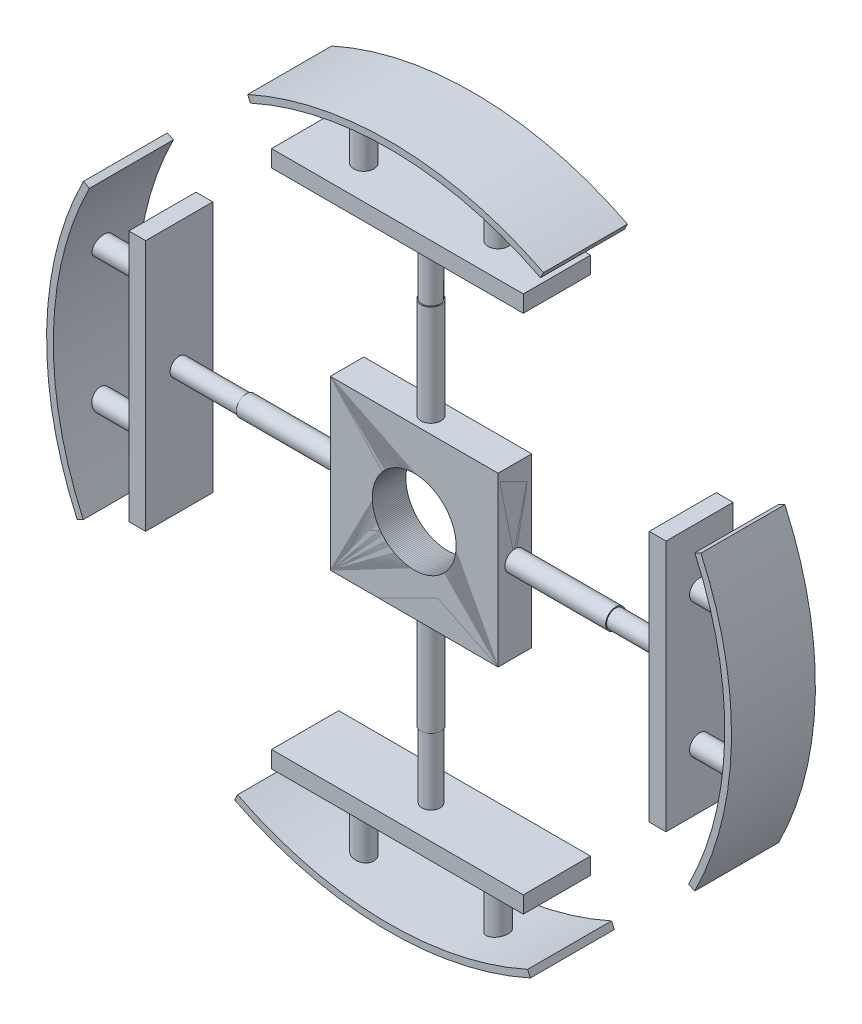
SolidWorks part; units mm, degrees
ref_plane "Front Plane" through (0, 0, 0) normal (0, 0, 1) x (1, 0, 0)
ref_plane "Top Plane" through (0, 0, 0) normal (0, 1, 0) x (1, 0, 0)
ref_plane "Right Plane" through (0, 0, 0) normal (1, 0, 0) x (0, 0, -1)
sketch "Sketch1" plane through (0, 0, 0) normal (0, 0, 1) x (1, 0, 0)
  line L1 (-25, 25) -> (25, 25)
  line L2 (-25, 25) -> (-25, -25)
  line L3 (-25, -25) -> (25, -25)
  line L4 (25, 25) -> (25, -25)
  line L5 (-25, 25) -> (25, -25) construction
  line L6 (-25, -25) -> (25, 25) construction
  point P0 (0, 0)
  dimension "D1" = 50
  dimension "D2" = 50
extrude "Boss-Extrude1" add sketch "Sketch1" along normal mid plane 10
sketch "Sketch2" plane through (0, 0, 0) normal (0, 0, 1) x (1, 0, 0)
  circle A0 centre (0, 0) radius 12.5
extrude "Cut-Extrude1" cut sketch "Sketch2" against normal mid plane 10
sketch "Sketch4" plane through (0, 25, 0) normal (0, 1, 0) x (1, 0, 0)
  circle A0 centre (0, 0) radius 3
extrude "Boss-Extrude2" add sketch "Sketch4" along normal blind 30
sketch "Sketch5" plane through (0, 55, 0) normal (0, 1, 0) x (1, 0, 0)
  circle A0 centre (0, 0) radius 2.7
extrude "Cut-Extrude2" cut sketch "Sketch5" against normal blind 30
sketch "Sketch6" plane through (0, 25, 0) normal (0, 1, 0) x (1, 0, 0)
  circle A1 centre (0, 0) radius 2.7
  circle A2 centre (0, 0) radius 2.7
  dimension "D1" = 0
extrude "Boss-Extrude3" add sketch "Sketch6" along normal blind 50
sketch "Sketch8" plane through (0, 0, 0) normal (0, 0, 1) x (1, 0, 0)
  line L0 (0, 99.0014) -> (0, -49.6038) construction
  line L3 (-37.5, 80) -> (37.5, 80)
  line L4 (-37.5, 80) -> (-37.5, 75)
  line L5 (-37.5, 75) -> (37.5, 75)
  line L6 (37.5, 80) -> (37.5, 75)
  line L7 (-37.5, 80) -> (16.5799, 76.3947) construction
  line L8 (-37.5, 75) -> (37.5, 80) construction
  point P6 (0, 77.5)
  dimension "D1" = 75
  dimension "D2" = 5
extrude "Boss-Extrude4" add sketch "Sketch8" along normal mid plane 20
sketch "Sketch9" plane through (0, 80, 0) normal (0, 1, 0) x (1, 0, 0)
  line L0 (-43.4012, 0) -> (57.5449, 0) construction
  line L1 (0, 17.0938) -> (0, -21.1348) construction
  line L2 (-20, 17.0938) -> (-20, -21.9484)
  line L3 (20, 17.0938) -> (20, -21.9604)
  circle A0 centre (-20, 0) radius 3
  circle A1 centre (20, 0) radius 3
  dimension "D1" = 20
  dimension "D2" = 20
sketch "Sketch10" plane through (0, 0, 0) normal (0, 0, 1) x (1, 0, 0)
  line L0 (46.0258, 91.0254) -> (45.1233, 89.2406)
  line L1 (-42.1017, 92.9056) -> (-41.2762, 91.0839)
  arc A0 (45.1233, 89.2406) -> (-41.2762, 91.0839) centre (0, 0) ccw
  arc A1 (46.0258, 91.0254) -> (-42.1017, 92.9056) centre (0, 0) ccw
  dimension "D1" = 2
extrude "Boss-Extrude5" add sketch "Sketch10" along normal mid plane 25 separate body
extrude "Boss-Extrude6" add sketch "Sketch9" along normal up to surface (17.9796 mm away) contours A0 up to face at (2.0283, 95.0698, 0)
extrude "Boss-Extrude7" add sketch "Sketch9<3>" along normal up to surface (17.9796 mm away) contours A1 up to face at (2.0283, 95.0698, 0)
sketch "Sketch9<3>" plane through (0, 80, 0) normal (0, 1, 0) x (1, 0, 0) same geometry as "Sketch9"
sketch "Sketch16" plane through (0, 0, 0) normal (0, 1, 0) x (1, 0, 0)
  line L0 (0, 0) -> (0, 122.8379) construction
pattern_circular "CirPattern5" count 4 over 360 about axis through (0, 0, 0) along (0, 0, -1) of bodies 109
